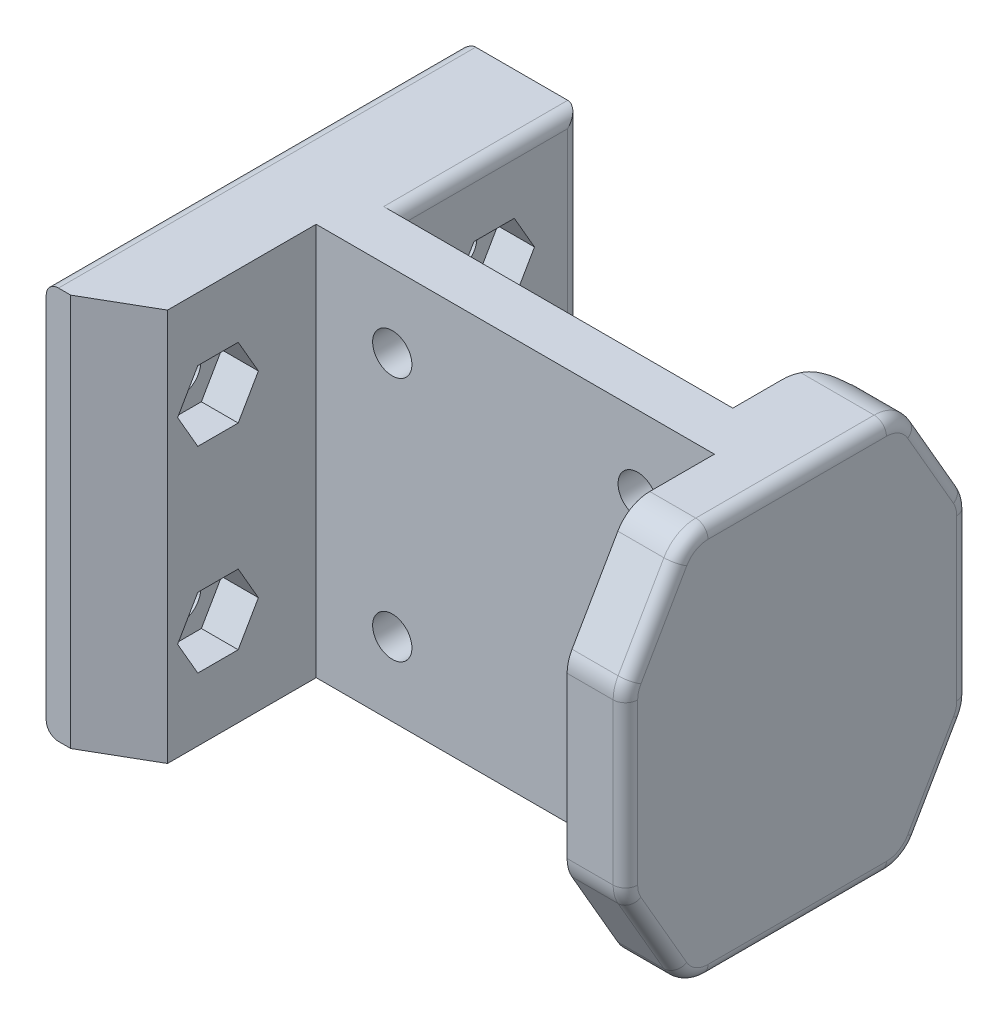
SolidWorks part; units mm, degrees
ref_plane "Спереди" through (0, 0, 0) normal (0, 0, 1) x (1, 0, 0)
ref_plane "Сверху" through (0, 0, 0) normal (0, 1, 0) x (1, 0, 0)
ref_plane "Справа" through (0, 0, 0) normal (1, 0, 0) x (0, 0, -1)
sketch "Эскиз1" plane through (0, 0, 0) normal (0, 0, 1) x (1, 0, 0)
  line L0 (0, 0) -> (36, 0)
  line L1 (0, 0) -> (0, 32)
  line L2 (36, 0) -> (36, 32)
  line L3 (0, 32) -> (36, 32)
  line L4 (18, 32) -> (18, 0) construction
  line L5 (36, 16) -> (0, 16) construction
  line L6 (8, 26) -> (8, 6) construction
  line L7 (8, 26) -> (28, 26) construction
  line L8 (28, 26) -> (28, 6) construction
  line L9 (28, 6) -> (8, 6) construction
  line L10 (8, 16) -> (28, 16) construction
  line L11 (18, 26) -> (18, 6) construction
  circle A0 centre (8, 26) radius 1.6
  circle A1 centre (28, 26) radius 1.6
  circle A2 centre (8, 6) radius 1.6
  circle A3 centre (28, 6) radius 1.6
  dimension "D1" = 20
  dimension "D2" = 20
  dimension "D3" = 3.2
  dimension "D4" = 3.2
  dimension "D5" = 3.2
  dimension "D6" = 3.2
  dimension "D7" = 32
  dimension "D8" = 36
extrude "Бобышка-Вытянуть1" add sketch "Эскиз1" along normal blind 4
sketch "Эскиз6" plane through (0, 32, 0) normal (0, 1, 0) x (1, 0, 0)
  line L0 (-5.2, -4) -> (-5.2, 24.8582) construction
  line L1 (36, -4) -> (0, -4) construction
  line L2 (36, -4) -> (36, 0) construction
  line L3 (-7.2, -4) -> (-7.2, 26.2382) construction
  dimension "D1" = 41.2
  dimension "D2" = 2
sketch "Эскиз7" plane through (0, 32, 0) normal (0, 1, 0) x (1, 0, 0)
  line L0 (0, 0) -> (-1.2, 0)
  line L1 (-1.2, 0) -> (-1.2, 15)
  line L3 (0, -4) -> (-1.2, -4)
  line L4 (-1.2, -4) -> (-1.2, -19)
  line L5 (-1.2, -19) -> (-5.2, -19)
  line L6 (-5.2, -19) -> (-5.2, 15)
  line L7 (-5.2, 15) -> (-1.2, 15)
  line L8 (-5.2, -4) -> (-5.2, 24.8582) construction
  line L9 (0, -4) -> (0, 0)
  dimension "D1" = 4
  dimension "D2" = 15
  dimension "D3" = 15
extrude "Бобышка-Вытянуть2" add sketch "Эскиз7" against normal up to surface (32 mm away) up to face at (18, 0, 2)
sketch "Эскиз8" plane through (-1.2, 0, 0) normal (1, 0, 0) x (0, 0, -1)
  line L0 (8, 24) -> (-12, 24) construction
  line L3 (8, 24) -> (8, 8) construction
  line L4 (-12, 24) -> (-12, 8) construction
  line L5 (8, 8) -> (-12, 8) construction
  line L6 (-4, 0) -> (-4, 32) construction
  line L7 (-4, 0) -> (-19, 0) construction
  line L8 (-19, 32) -> (-4, 32) construction
  circle A0 centre (8, 24) radius 1.6
  circle A1 centre (8, 8) radius 1.6
  circle A2 centre (-12, 8) radius 1.6
  circle A3 centre (-12, 24) radius 1.6
  dimension "D7" = 3.2
  dimension "D8" = 3.2
  dimension "D9" = 3.2
  dimension "D10" = 3.2
  dimension "D1" = 20
  dimension "D2" = 8
  dimension "D3" = 8
  dimension "D4" = 16
  dimension "D5" = 8
  dimension "D6" = 8
extrude "Вырез-Вытянуть1" cut sketch "Эскиз8" against normal through all
sketch "Sketch1" plane through (36, 0, 0) normal (1, 0, 0) x (0, 0, -1)
  line L4 (0, 0) -> (0, 32)
  line L5 (0, 32) -> (-4, 32)
  line L6 (-4, 32) -> (-4, 0)
  line L7 (-4, 0) -> (0, 0)
  line L8 (0, 0) -> (0, 32)
  line L9 (0, 32) -> (-4, 32)
  line L10 (-4, 32) -> (-4, 0)
  line L11 (-4, 0) -> (0, 0)
  dimension "D1" = 0
extrude "Boss-Extrude1" add sketch "Sketch1" along normal blind 3
sketch "Sketch2" plane through (0, 0, 0) normal (0, 0, -1) x (-1, 0, 0)
  line L0 (-39, 32) -> (-34, 32)
  line L1 (-39, 32) -> (-39, 0)
  line L2 (-34, 32) -> (-34, 0)
  line L3 (-39, 0) -> (-34, 0)
  line L4 (-39, 32) -> (1.2, 32) construction
  line L5 (1.2, 0) -> (-39, 0) construction
  dimension "D1" = 5
extrude "Boss-Extrude2" add sketch "Sketch2" along normal blind 12
sketch "Sketch3" plane through (39, 0, 0) normal (1, 0, 0) x (0, 0, -1)
  line L0 (0, 0) -> (0, 32) construction
  line L1 (0, 0) -> (0, 32) construction
  line L2 (0, 32) -> (7, 32) construction
  line L3 (12, 32) -> (-4, 32) construction
  line L4 (7, 32) -> (12, 23.3397) construction
  line L5 (12, 32) -> (12, 0) construction
  line L6 (0, 16) -> (12, 16) construction
  line L7 (12, 23.3397) -> (12, 8.6603) construction
  line L8 (7, 0) -> (12, 8.6603) construction
  line L9 (7, 32) -> (12, 32)
  line L10 (12, 32) -> (12, 23.3397)
  line L11 (12, 23.3397) -> (7, 32)
  line L12 (7, 0) -> (12, 8.6603) construction
  line L13 (0, 0) -> (7, 0) construction
  line L14 (12, 8.6603) -> (7, 0)
  line L15 (12, 0) -> (12, 8.6603)
  line L16 (7, 0) -> (12, 0)
  dimension "D1" = 120
  dimension "D2" = 7
extrude "Cut-Extrude1" cut sketch "Sketch3" against normal up to surface (5 mm away) up to face at (34, 16, -6)
sketch "Sketch6" plane through (39, 0, 0) normal (1, 0, 0) x (0, 0, -1)
  line L0 (7, 32) -> (0, 32) construction
  line L1 (7, 32) -> (0, 32) construction
  line L2 (7, 0) -> (0, 0) construction
  line L3 (7, 0) -> (0, 0) construction
  line L4 (0, 32) -> (0, 0) construction
  line L5 (-4, 32) -> (0, 32) construction
  line L6 (-4, 0) -> (0, 0) construction
  line L7 (-2, 32) -> (-2, 0) construction
  line L8 (12, 8.6603) -> (7, 0) construction
  line L9 (7, 32) -> (12, 23.3397) construction
  line L10 (12, 23.3397) -> (12, 8.6603) construction
  line L11 (7, 32) -> (12, 23.3397) construction
  line L12 (12, 23.3397) -> (12, 8.6603) construction
  line L13 (12, 8.6603) -> (7, 0) construction
  line L14 (-16, 8.6603) -> (-11, 0)
  line L15 (-16, 23.3397) -> (-16, 8.6603)
  line L16 (-11, 32) -> (-16, 23.3397)
  line L17 (-11, 32) -> (-4, 32)
  line L18 (-4, 32) -> (-4, 0)
  line L19 (-4, 0) -> (-11, 0)
extrude "Boss-Extrude5" add sketch "Sketch6" against normal blind 5
sketch "Sketch7" plane through (-1.2, 0, 0) normal (1, 0, 0) x (0, 0, -1)
  line L4 (0, 0) -> (15, 0)
  line L5 (15, 0) -> (15, 32)
  line L6 (15, 32) -> (0, 32)
  line L7 (0, 32) -> (0, 0)
  line L8 (0, 0) -> (15, 0)
  line L9 (15, 0) -> (15, 32)
  line L10 (15, 32) -> (0, 32)
  line L11 (0, 32) -> (0, 0)
  line L12 (-19, 0) -> (-4, 0)
  line L13 (-4, 0) -> (-4, 32)
  line L14 (-4, 32) -> (-19, 32)
  line L15 (-19, 32) -> (-19, 0)
  line L16 (-19, 0) -> (-4, 0)
  line L17 (-4, 0) -> (-4, 32)
  line L18 (-4, 32) -> (-19, 32)
  line L19 (-19, 32) -> (-19, 0)
  circle A0 centre (-12, 24) radius 1.6 construction
  circle A1 centre (-12, 8) radius 1.6 construction
  circle A2 centre (8, 24) radius 1.6 construction
  circle A3 centre (8, 8) radius 1.6 construction
  circle A4 centre (-12, 24) radius 1.6
  circle A5 centre (-12, 8) radius 1.6
  circle A6 centre (8, 24) radius 1.6
  circle A7 centre (8, 8) radius 1.6
  dimension "D1" = 0
  dimension "D2" = 0
extrude "Boss-Extrude6" add sketch "Sketch7" along normal blind 3
sketch "Sketch8" plane through (34, 0, 0) normal (-1, 0, 0) x (0, 0, 1)
  line L0 (-12, 23.3397) -> (-12, 8.6603) construction
  line L1 (-12, 8.6603) -> (-7, 0) construction
  line L2 (-7, 0) -> (0, 0) construction
  line L3 (0, 0) -> (0, 32) construction
  line L4 (0, 32) -> (-7, 32) construction
  line L5 (-7, 32) -> (-12, 23.3397) construction
  line L6 (4, 32) -> (4, 0) construction
  line L7 (4, 0) -> (11, 0) construction
  line L8 (11, 0) -> (16, 8.6603) construction
  line L9 (16, 8.6603) -> (16, 23.3397) construction
  line L10 (16, 23.3397) -> (11, 32) construction
  line L11 (11, 32) -> (4, 32) construction
  line L12 (-12, 23.3397) -> (-12, 8.6603)
  line L13 (-12, 8.6603) -> (-7, 0)
  line L14 (-7, 0) -> (0, 0)
  line L15 (0, 0) -> (0, 32)
  line L16 (0, 32) -> (-7, 32)
  line L17 (-7, 32) -> (-12, 23.3397)
  line L18 (4, 32) -> (4, 0)
  line L19 (4, 0) -> (11, 0)
  line L20 (11, 0) -> (16, 8.6603)
  line L21 (16, 8.6603) -> (16, 23.3397)
  line L22 (16, 23.3397) -> (11, 32)
  line L23 (11, 32) -> (4, 32)
extrude "Cut-Extrude2" cut sketch "Sketch8" against normal blind 0.25
sketch "Sketch9" plane through (1.8, 0, 0) normal (1, 0, 0) x (0, 0, -1)
  line L4 (0, 32) -> (0, 0)
  line L5 (0, 0) -> (15, 0)
  line L6 (15, 0) -> (15, 32)
  line L7 (15, 32) -> (0, 32)
  line L8 (0, 32) -> (0, 0)
  line L9 (0, 0) -> (15, 0)
  line L10 (15, 0) -> (15, 32)
  line L11 (15, 32) -> (0, 32)
  circle A0 centre (8, 24) radius 1.6 construction
  circle A1 centre (8, 8) radius 1.6 construction
  circle A2 centre (8, 24) radius 1.6
  circle A3 centre (8, 8) radius 1.6
  dimension "D1" = 0
extrude "Boss-Extrude7" add sketch "Sketch9" along normal blind 2.5
sketch "Sketch10" plane through (34.25, 0, 0) normal (-1, 0, 0) x (0, 0, 1)
  line L6 (-7, 32) -> (-12, 23.3397)
  line L7 (-12, 23.3397) -> (-12, 8.6603)
  line L8 (-12, 8.6603) -> (-7, 0)
  line L9 (-7, 0) -> (0, 0)
  line L10 (0, 0) -> (0, 32)
  line L11 (0, 32) -> (-7, 32)
  line L12 (-7, 32) -> (-12, 23.3397)
  line L13 (-12, 23.3397) -> (-12, 8.6603)
  line L14 (-12, 8.6603) -> (-7, 0)
  line L15 (-7, 0) -> (0, 0)
  line L16 (0, 0) -> (0, 32)
  line L17 (0, 32) -> (-7, 32)
  dimension "D1" = 0
extrude "Boss-Extrude8" add sketch "Sketch10" along normal blind 2.5
sketch "Sketch11" plane through (31.75, 0, 0) normal (-1, 0, 0) x (0, 0, 1)
  line L0 (-7, 32) -> (-12, 23.3397) construction
  line L1 (-12, 23.3397) -> (-12, 8.6603) construction
  line L2 (-12, 8.6603) -> (-7, 0) construction
  line L3 (-7, 32) -> (-12, 23.3397)
  line L4 (-12, 23.3397) -> (-12, 8.6603)
  line L5 (-12, 8.6603) -> (-7, 0)
  line L6 (-7, 32) -> (-7, 0)
extrude "Cut-Extrude3" cut sketch "Sketch11" against normal blind 2.5
fillet "Fillet2" radius 3 1 edges at (31.75, 16, -7)
fillet "Fillet4" radius 3 4 edges at (36.625, 0, -7) (36.625, 8.6603, -12) (36.625, 23.3397, -12) (36.625, 32, -7)
fillet "Fillet5" radius 3 4 edges at (36.625, 0, 11) (36.625, 8.6603, 16) (36.625, 23.3397, 16) (36.625, 32, 11)
fillet "Fillet9" radius 1 16 edges at (39, 8.6876, 15.8978) (39, 16, 16) (39, 23.3124, 15.8978) (39, 27.2679, 13.7321) (39, 31.5981, 10.7679) (39, 32, 2) (39, 31.5981, -6.7679) (39, 27.2679, -9.7321) (39, 23.3124, -11.8978) (39, 16, -12) (39, 8.6876, -11.8978) (39, 4.7321, -9.7321) (39, 0.4019, -6.7679) (39, 0, 2) (39, 0.4019, 10.7679) (39, 4.7321, 13.7321)
sketch "Sketch12" plane through (4.3, 0, 0) normal (1, 0, 0) x (0, 0, -1)
  line L0 (11.2909, 24) -> (4.7091, 24) construction
  line L1 (6.3546, 26.85) -> (4.7091, 24)
  line L2 (4.7091, 24) -> (6.3546, 21.15)
  line L3 (6.3546, 21.15) -> (9.6454, 21.15)
  line L4 (9.6454, 21.15) -> (11.2909, 24)
  line L5 (11.2909, 24) -> (9.6454, 26.85)
  line L6 (9.6454, 26.85) -> (6.3546, 26.85)
  line L7 (11.2909, 8) -> (4.7091, 8) construction
  line L8 (6.3546, 10.85) -> (4.7091, 8)
  line L9 (4.7091, 8) -> (6.3546, 5.15)
  line L10 (6.3546, 5.15) -> (9.6454, 5.15)
  line L11 (9.6454, 5.15) -> (11.2909, 8)
  line L12 (11.2909, 8) -> (9.6454, 10.85)
  line L13 (9.6454, 10.85) -> (6.3546, 10.85)
  circle A0 centre (8, 24) radius 2.85 construction
  circle A1 centre (8, 8) radius 2.85 construction
  dimension "D1" = 5.7
  dimension "D2" = 5.7
extrude "Cut-Extrude4" cut sketch "Sketch12" against normal blind 3
sketch "Sketch13" plane through (1.8, 0, 0) normal (1, 0, 0) x (0, 0, -1)
  line L0 (-8.7091, 24) -> (-15.2909, 24) construction
  line L1 (-15.2909, 24) -> (-13.6454, 21.15)
  line L2 (-13.6454, 21.15) -> (-10.3546, 21.15)
  line L3 (-10.3546, 21.15) -> (-8.7091, 24)
  line L4 (-8.7091, 24) -> (-10.3546, 26.85)
  line L5 (-10.3546, 26.85) -> (-13.6454, 26.85)
  line L6 (-13.6454, 26.85) -> (-15.2909, 24)
  line L7 (-15.2909, 8) -> (-13.6454, 5.15)
  line L8 (-13.6454, 5.15) -> (-10.3546, 5.15)
  line L9 (-10.3546, 5.15) -> (-8.7091, 8)
  line L10 (-8.7091, 8) -> (-10.3546, 10.85)
  line L11 (-10.3546, 10.85) -> (-13.6454, 10.85)
  line L12 (-13.6454, 10.85) -> (-15.2909, 8)
  line L13 (-8.7091, 8) -> (-15.2909, 8) construction
  circle A0 centre (-12, 24) radius 2.85 construction
  circle A1 centre (-12, 8) radius 2.85 construction
  dimension "D1" = 5.7
  dimension "D2" = 5.7
extrude "Cut-Extrude5" cut sketch "Sketch13" against normal blind 3
fillet "Fillet14" radius 1 6 edges at (4.3, 32, -7.5) (4.3, 0, -7.5) (4.3, 16, -15) (-5.2, 0, 2) (-5.2, 16, -15) (-5.2, 32, 2)
chamfer "Фаска1" distance 5 angle 30 1 edges at (1.8, 16, 19) first distance on face at (-2.6024, 16, 19)
